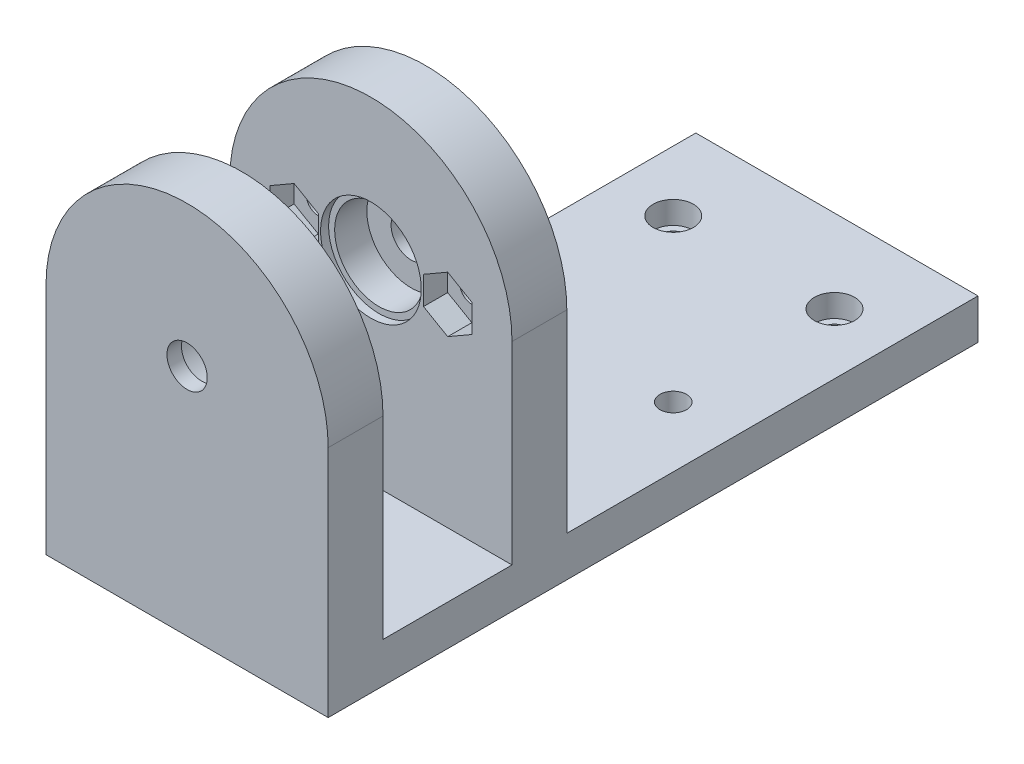
SolidWorks part; units mm, degrees
ref_plane "Front Plane" through (0, 0, 0) normal (0, 0, 1) x (1, 0, 0)
ref_plane "Top Plane" through (0, 0, 0) normal (0, 1, 0) x (1, 0, 0)
ref_plane "Right Plane" through (0, 0, 0) normal (1, 0, 0) x (0, 0, -1)
sketch "Sketch1" plane through (0, 0, 0) normal (0, 1, 0) x (1, 0, 0)
  line L0 (-27.381, 0) -> (53.0952, 0) construction
  line L1 (0, 33.6905) -> (0, -17.5) construction
  line L2 (-10, 20) -> (10, 20) construction
  line L3 (-10, 10) -> (10, 10) construction
  line L4 (-10, 10) -> (-10, 30) construction
  line L5 (-10, 30) -> (10, 30) construction
  line L6 (10, 10) -> (10, 30) construction
  line L7 (-10, 10) -> (10, 30) construction
  line L8 (-10, 30) -> (10, 10) construction
  line L9 (-10, -30) -> (10, -30) construction
  line L10 (-10, -30) -> (10, -10) construction
  line L11 (-10, -20) -> (10, -20) construction
  line L12 (-10, -10) -> (-10, -30) construction
  line L13 (-10, -10) -> (10, -30) construction
  line L14 (-10, -10) -> (10, -10) construction
  line L15 (10, -10) -> (10, -30) construction
  line L16 (-17.5, -33.5) -> (17.5, -6.5) construction
  line L17 (-17.5, 6.5) -> (17.5, 6.5) construction
  line L18 (-17.5, 6.5) -> (-17.5, 33.5) construction
  line L19 (-17.5, 33.5) -> (17.5, 33.5) construction
  line L20 (17.5, 6.5) -> (17.5, 33.5) construction
  line L21 (-17.5, 6.5) -> (17.5, 33.5) construction
  line L22 (-17.5, 33.5) -> (17.5, 6.5) construction
  line L23 (-17.5, -6.5) -> (-17.5, -33.5) construction
  line L24 (-17.5, -33.5) -> (17.5, -33.5) construction
  line L25 (17.5, -6.5) -> (17.5, -33.5) construction
  line L26 (-17.5, -6.5) -> (17.5, -6.5) construction
  line L27 (-17.5, -6.5) -> (17.5, -33.5) construction
  line L34 (-17.5, -40.3) -> (17.5, -40.3)
  line L35 (-17.5, 40.3) -> (17.5, 40.3)
  line L36 (-17.5, 40.3) -> (-17.5, -40.3)
  line L37 (17.5, 40.3) -> (17.5, -40.3)
  circle A0 centre (-10, 30) radius 1.65
  circle A1 centre (10, 30) radius 1.65
  circle A2 centre (10, 10) radius 1.65
  circle A3 centre (-10, 10) radius 1.65
  circle A4 centre (-10, -10) radius 1.65 construction
  circle A5 centre (10, -10) radius 1.65 construction
  circle A6 centre (10, -30) radius 1.65
  circle A7 centre (-10, -30) radius 1.65
  point P4 (0, 20)
  point P26 (0, 20)
  dimension "D3" = 3.3
  dimension "D1" = 20
  dimension "D2" = 40
  dimension "D4" = 35
  dimension "D5" = 27
  dimension "D6" = 6.8
  dimension "D7" = 6.8
  dimension "D8" = 30.3
  dimension "D9" = 10.3
  dimension "D10" = 7.5
extrude "Boss-Extrude1" add sketch "Sketch1" along normal blind 5
sketch "Sketch2" plane through (0, 5, 0) normal (0, 1, 0) x (1, 0, 0)
  circle A0 centre (-10, 30) radius 2.5
  circle A1 centre (10, 30) radius 2.5
  circle A9 centre (-10, -30) radius 2.5
  circle A10 centre (10, -30) radius 2.5
  dimension "D1" = 5
extrude "Cut-Extrude1" cut sketch "Sketch2" against normal blind 2.8
ref_plane "Plane1" through (0, 0, 33.5) normal (0, 0, 1) x (1, 0, 0)
sketch "Sketch3" plane through (0, 0, 33.5) normal (0, 0, 1) x (1, 0, 0)
  line L0 (-17.5, 5) -> (17.5, 5)
  line L1 (17.5, 5) -> (17.5, 29)
  line L2 (-17.5, 5) -> (-17.5, 29)
  arc A0 (-17.5, 29) -> (17.5, 29) centre (0, 29) cw
  circle A1 centre (0, 29) radius 2.5
  point P2 (0, 0)
  point P3 (-17.5, 5)
  point P8 (0, 0)
  point P9 (0, 0)
  point P10 (0, 0)
  point P11 (15.8489, 5)
  point P12 (0, 0)
  dimension "D1" = 5
  dimension "D2" = 24
extrude "Boss-Extrude2" add sketch "Sketch3" along normal blind 6.8
sketch "Sketch4" plane through (0, 0, 33.5) normal (0, 0, -1) x (-1, 0, 0)
  circle A0 centre (0, 29) radius 6.25
  dimension "D1" = 12.5
extrude "Cut-Extrude2" cut sketch "Sketch4" against normal blind 1
sketch "Sketch5" plane through (0, 0, 34.5) normal (0, 0, -1) x (-1, 0, 0)
  circle A0 centre (0, 29) radius 5.5
  dimension "D1" = 11
extrude "Cut-Extrude3" cut sketch "Sketch5" against normal blind 4
ref_plane "Mirror Plane" through (0, 0, 25.5) normal (0, 0, 1) x (1, 0, 0)
mirror "Mirror1" about plane through (0, 0, 25.5) normal (0, 0, 1) of "Cut-Extrude3", "Cut-Extrude2", "Boss-Extrude2"
sketch "Sketch6" plane through (0, 0, 10.7) normal (0, 0, -1) x (-1, 0, 0)
  line L0 (-9.525, 29) -> (9.525, 29) construction
  line L1 (0, 38.525) -> (0, 19.475) construction
  circle A0 centre (0, 29) radius 9.525 construction
  circle A1 centre (-9.525, 29) radius 1.5
  circle A2 centre (9.525, 29) radius 1.5
  dimension "D1" = 19.05
  dimension "D2" = 3
extrude "Cut-Extrude4" cut sketch "Sketch6" against normal up to surface (6.8 mm away) up to face at (-6.25, 29, 17.5)
sketch "Sketch7" plane through (0, 0, 17.5) normal (0, 0, 1) x (1, 0, 0)
  line L0 (0, 0) -> (0, 46.5) construction
  line L1 (-12.525, 30.7321) -> (-12.525, 27.2679)
  line L2 (-12.525, 27.2679) -> (-9.525, 25.5359)
  line L3 (-9.525, 25.5359) -> (-6.525, 27.2679)
  line L4 (-6.525, 27.2679) -> (-6.525, 30.7321)
  line L5 (-6.525, 30.7321) -> (-9.525, 32.4641)
  line L6 (-9.525, 32.4641) -> (-12.525, 30.7321)
  line L7 (9.525, 32.4641) -> (12.525, 30.7321)
  line L8 (6.525, 30.7321) -> (9.525, 32.4641)
  line L9 (6.525, 27.2679) -> (6.525, 30.7321)
  line L10 (9.525, 25.5359) -> (6.525, 27.2679)
  line L11 (12.525, 27.2679) -> (9.525, 25.5359)
  line L12 (12.525, 30.7321) -> (12.525, 27.2679)
  circle A0 centre (-9.525, 29) radius 3 construction
  arc A1 (17.5, 29) -> (-17.5, 29) centre (0, 29) ccw construction
  circle A2 centre (9.525, 29) radius 3 construction
  dimension "D1" = 6
extrude "Cut-Extrude5" cut sketch "Sketch7" against normal blind 3
